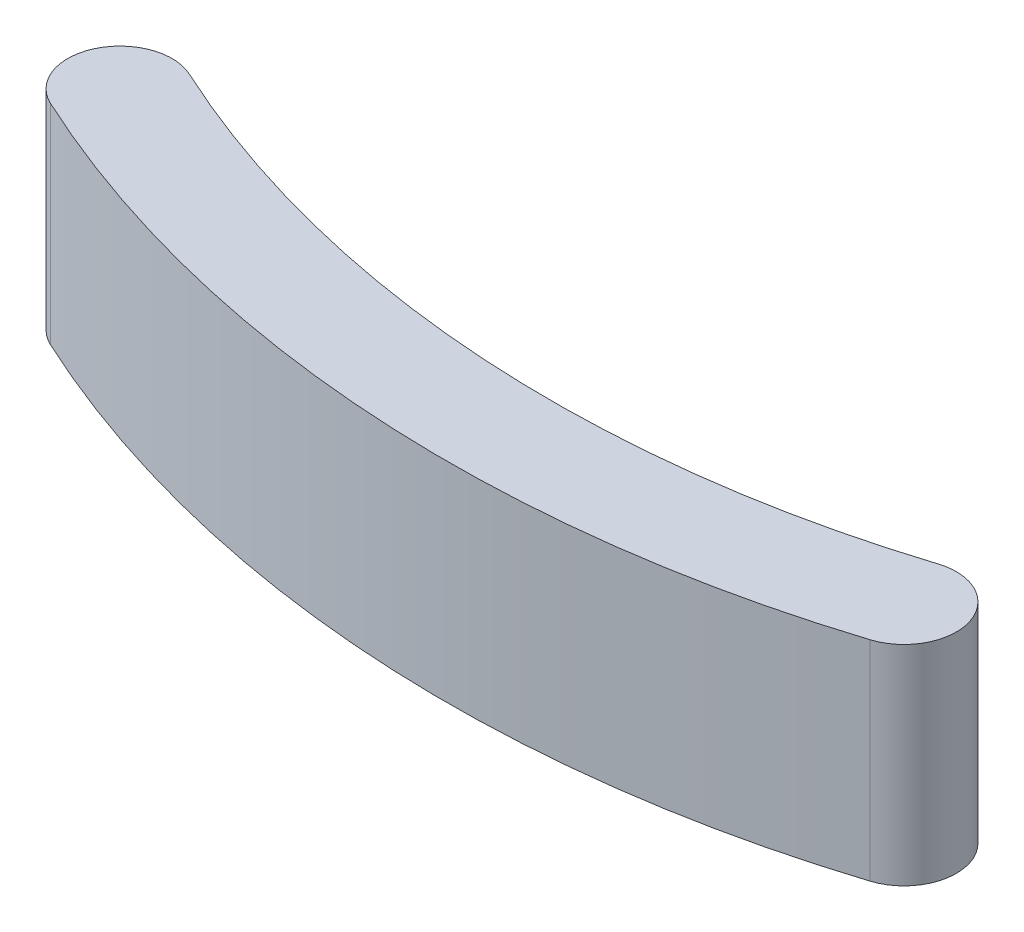
SolidWorks part; units mm, degrees
ref_plane "Front Plane" through (0, 0, 0) normal (0, 0, 1) x (1, 0, 0)
ref_plane "Top Plane" through (0, 0, 0) normal (0, 1, 0) x (1, 0, 0)
ref_plane "Right Plane" through (0, 0, 0) normal (1, 0, 0) x (0, 0, -1)
ref_axis "Axis1" through (0, 21, 0) along (0, -1, 0)
sketch "Sketch1" plane through (0, 0, 0) normal (0, 1, 0) x (1, 0, 0)
  line L0 (0, 0) -> (87.1854, 0) construction
  arc A0 (0, 0) -> (80, -5) centre (46.4323, 100.4167) ccw construction
  arc A5 (-2.0985, -4.5383) -> (81.5171, -9.7643) centre (46.4323, 100.4167) ccw
  arc A6 (2.0985, 4.5383) -> (78.4829, -0.2357) centre (46.4323, 100.4167) ccw
  arc A7 (2.0985, 4.5383) -> (-2.0985, -4.5383) centre (0, 0) ccw
  arc A8 (81.5171, -9.7643) -> (78.4829, -0.2357) centre (80, -5) ccw
  point P4 (39.5313, -10)
  dimension "D3" = 10
  dimension "D1" = 5
  dimension "D2" = 80
  dimension "D4" = 5
extrude "Boss-Extrude1" add sketch "Sketch1" along normal blind 20
